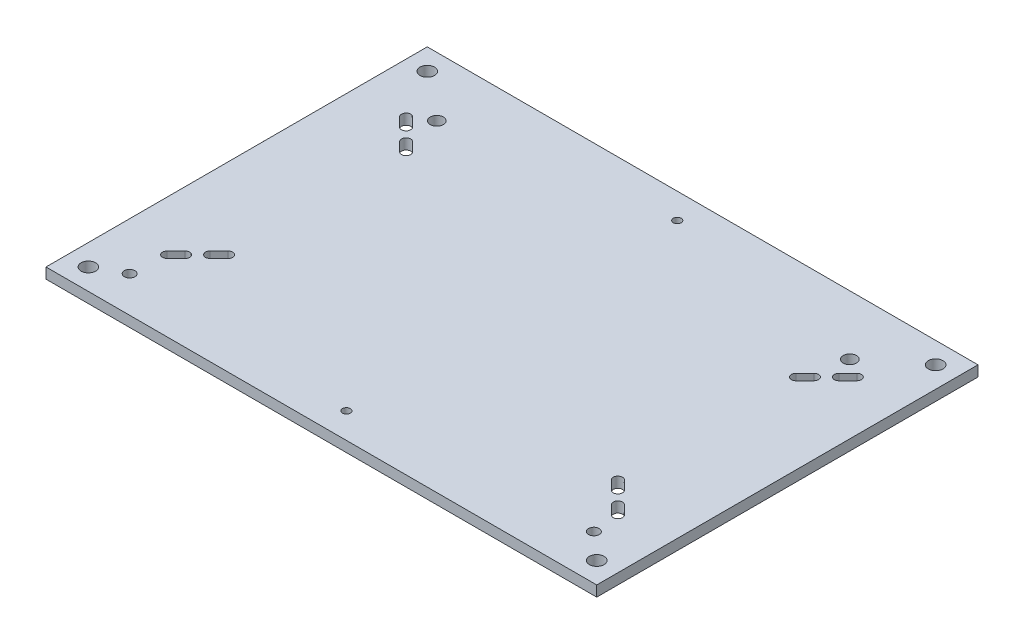
SolidWorks part; units mm, degrees
ref_plane "Front Plane" through (0, 0, 0) normal (0, 0, 1) x (1, 0, 0)
ref_plane "Top Plane" through (0, 0, 0) normal (0, 1, 0) x (1, 0, 0)
ref_plane "Right Plane" through (0, 0, 0) normal (1, 0, 0) x (0, 0, -1)
sketch "Sketch1" plane through (0, 0, 0) normal (0, 1, 0) x (1, 0, 0)
  line L1 (0, 0) -> (330.2, 0)
  line L2 (0, 0) -> (0, -228.6)
  line L3 (0, -228.6) -> (330.2, -228.6)
  line L4 (330.2, 0) -> (330.2, -228.6)
  dimension "D1" = 330.2
  dimension "D2" = 228.6
extrude "base plate" add sketch "Sketch1" against normal blind 6.35
sketch "center lines" plane through (0, 0, 0) normal (0, 1, 0) x (1, 0, 0)
  line L0 (165.1, 0) -> (165.1, -228.6) construction
  line L1 (330.2, 0) -> (0, 0) construction
  line L2 (0, -228.6) -> (330.2, -228.6) construction
  line L3 (0, -114.3) -> (330.2, -114.3) construction
  line L4 (0, 0) -> (0, -228.6) construction
  line L5 (330.2, -228.6) -> (330.2, 0) construction
sketch "Sketch3" plane through (0, 0, 0) normal (0, 1, 0) x (1, 0, 0)
  line L0 (21.0672, -185.8525) -> (30.0475, -194.8328)
  line L1 (30.0475, -194.8328) -> (60.5804, -164.2999)
  line L2 (60.5804, -164.2999) -> (51.6001, -155.3196)
  line L3 (51.6001, -155.3196) -> (21.0672, -185.8525)
  line L4 (29.9612, -185.9388) -> (35.3494, -180.5506) construction
  line L5 (28.0167, -183.9942) -> (33.4048, -178.6061)
  line L6 (31.9058, -187.8833) -> (37.2939, -182.4952)
  line L7 (0, -228.6) -> (330.2, -228.6) construction
  line L8 (48.2187, -167.6813) -> (42.8306, -173.0694) construction
  line L9 (50.1633, -169.6258) -> (44.7751, -175.014)
  line L10 (165.1, 0) -> (165.1, -228.6) construction
  line L11 (0, -114.3) -> (330.2, -114.3) construction
  line L12 (60.5804, -64.3001) -> (51.6001, -73.2804)
  line L13 (30.0475, -33.7672) -> (60.5804, -64.3001)
  line L14 (21.0672, -42.7475) -> (30.0475, -33.7672)
  line L15 (51.6001, -73.2804) -> (21.0672, -42.7475)
  line L16 (300.1525, -33.7672) -> (269.6196, -64.3001)
  line L17 (309.1328, -42.7475) -> (300.1525, -33.7672)
  line L18 (278.5999, -73.2804) -> (309.1328, -42.7475)
  line L19 (269.6196, -64.3001) -> (278.5999, -73.2804)
  line L20 (269.6196, -164.2999) -> (278.5999, -155.3196)
  line L21 (300.1525, -194.8328) -> (269.6196, -164.2999)
  line L22 (309.1328, -185.8525) -> (300.1525, -194.8328)
  line L23 (278.5999, -155.3196) -> (309.1328, -185.8525)
  line L24 (46.2742, -165.7367) -> (40.886, -171.1249)
  line L25 (29.9612, -42.6612) -> (35.3494, -48.0494) construction
  line L26 (28.0167, -44.6058) -> (33.4048, -49.9939)
  line L27 (31.9058, -40.7167) -> (37.2939, -46.1048)
  line L28 (48.2187, -60.9187) -> (42.8306, -55.5306) construction
  line L29 (50.1633, -58.9742) -> (44.7751, -53.586)
  line L30 (46.2742, -62.8633) -> (40.886, -57.4751)
  line L31 (300.2388, -42.6612) -> (294.8506, -48.0494) construction
  line L32 (302.1833, -44.6058) -> (296.7952, -49.9939)
  line L33 (298.2942, -40.7167) -> (292.9061, -46.1048)
  line L34 (281.9813, -60.9187) -> (287.3694, -55.5306) construction
  line L35 (280.0367, -58.9742) -> (285.4249, -53.586)
  line L36 (283.9258, -62.8633) -> (289.314, -57.4751)
  line L37 (281.9813, -167.6813) -> (287.3694, -173.0694) construction
  line L38 (280.0367, -169.6258) -> (285.4249, -175.014)
  line L39 (283.9258, -165.7367) -> (289.314, -171.1249)
  line L40 (300.2388, -185.9388) -> (294.8506, -180.5506) construction
  line L41 (302.1833, -183.9942) -> (296.7952, -178.6061)
  line L42 (298.2942, -187.8833) -> (292.9061, -182.4952)
  line L43 (51.6001, -164.2999) -> (51.6001, -155.3196)
  line L44 (60.5804, -164.2999) -> (51.6001, -164.2999)
  line L45 (51.6001, -64.3001) -> (51.6001, -73.2804)
  line L46 (60.5804, -64.3001) -> (51.6001, -64.3001)
  line L47 (278.5999, -64.3001) -> (278.5999, -73.2804)
  line L48 (269.6196, -64.3001) -> (278.5999, -64.3001)
  line L49 (278.5999, -164.2999) -> (278.5999, -155.3196)
  line L50 (269.6196, -164.2999) -> (278.5999, -164.2999)
  arc A0 (28.0167, -183.9942) -> (31.9058, -187.8833) centre (29.9612, -185.9388) ccw
  arc A1 (37.2939, -182.4952) -> (33.4048, -178.6061) centre (35.3494, -180.5506) ccw
  arc A2 (50.1633, -169.6258) -> (46.2742, -165.7367) centre (48.2187, -167.6813) ccw
  arc A3 (40.886, -171.1249) -> (44.7751, -175.014) centre (42.8306, -173.0694) ccw
  arc A4 (28.0167, -44.6058) -> (31.9058, -40.7167) centre (29.9612, -42.6612) cw
  arc A5 (37.2939, -46.1048) -> (33.4048, -49.9939) centre (35.3494, -48.0494) cw
  arc A6 (50.1633, -58.9742) -> (46.2742, -62.8633) centre (48.2187, -60.9187) cw
  arc A7 (40.886, -57.4751) -> (44.7751, -53.586) centre (42.8306, -55.5306) cw
  arc A8 (302.1833, -44.6058) -> (298.2942, -40.7167) centre (300.2388, -42.6612) ccw
  arc A9 (292.9061, -46.1048) -> (296.7952, -49.9939) centre (294.8506, -48.0494) ccw
  arc A10 (280.0367, -58.9742) -> (283.9258, -62.8633) centre (281.9813, -60.9187) ccw
  arc A11 (289.314, -57.4751) -> (285.4249, -53.586) centre (287.3694, -55.5306) ccw
  arc A12 (280.0367, -169.6258) -> (283.9258, -165.7367) centre (281.9813, -167.6813) cw
  arc A13 (289.314, -171.1249) -> (285.4249, -175.014) centre (287.3694, -173.0694) cw
  arc A14 (302.1833, -183.9942) -> (298.2942, -187.8833) centre (300.2388, -185.9388) cw
  arc A15 (292.9061, -182.4952) -> (296.7952, -178.6061) centre (294.8506, -180.5506) cw
  point P29 (32.6553, -183.2447)
  point P36 (45.5246, -170.3754)
  point P44 (32.6553, -45.3553)
  point P51 (45.5246, -58.2246)
  point P58 (297.5447, -45.3553)
  point P65 (284.6754, -58.2246)
  point P72 (284.6754, -170.3754)
  point P79 (297.5447, -183.2447)
  point P84 (37.2939, -178.6061)
  point P85 (40.886, -175.014)
  dimension "D6" = 2.75
  dimension "D10" = 5.08
  dimension "D9" = 2.032
  dimension "D1" = 43.18
  dimension "D2" = 12.7
  dimension "D3" = 45
  dimension "D4" = 99.9998
  dimension "D5" = 226.9998
  dimension "D7" = 7.62
  dimension "D8" = 6.35
extrude "slots" cut sketch "Sketch3" against normal through all contours A5 L27 A4 L26 | L33 A9 L32 A8 | L36 A11 L35 A10 | A13 L39 A12 L38 | A15 L42 A14 L41 | L6 A1 L5 A0 | L24 A3 L9 A2 | L30 A7 L29 A6 region at (32.6553, 0, 45.3553) region at (297.5447, 0, 45.3553) region at (284.6754, 0, 58.2246) region at (284.6754, 0, 170.3754) region at (297.5447, 0, 183.2447)
sketch "location of ESD" plane through (0, 0, 0) normal (0, 1, 0) x (1, 0, 0)
  line L0 (330.2, -228.6) -> (330.2, 0) construction
  line L1 (330.2, 0) -> (0, 0) construction
  point P0 (304.8, -114.3)
  point P3 (330.2, -114.3)
  dimension "D1" = 25.4
  dimension "D2" = 114.3
hole_wizard "Feet connection hole" positions "Sketch6" profile "Sketch7" hole size "1/4-20" standard "PEM® Inch" end condition through all
sketch "Sketch6" plane through (0, 0, 0) normal (0, 1, 0) x (1, 0, 0)
  line L0 (0, -228.6) -> (330.2, -228.6) construction
  line L1 (0, 0) -> (0, -228.6) construction
  line L2 (330.2, -228.6) -> (330.2, 0) construction
  line L3 (330.2, 0) -> (0, 0) construction
  point P3 (12.7, -215.9)
  point P19 (317.5, -12.7)
  point P31 (317.5, -215.9)
  point P33 (12.7, -12.7)
  dimension "D1" = 12.7
  dimension "D2" = 12.7
  dimension "D3" = 12.7
  dimension "D4" = 12.7
sketch "Sketch7" plane through (12.7, 0, 215.9) normal (1, 0, 0) x (0, 0, 1)
  line L0 (0, 0) -> (0, 6.35)
  line L1 (0, 6.35) -> (4.3688, 6.35)
  line L2 (4.3688, 6.35) -> (4.3688, 0)
  line L5 (4.3688, 0) -> (0, 0)
  line L11 (0, -6.35) -> (0, 107.95) construction
  dimension "Thru Hole Dia." = 8.7376
  dimension "Thru Hole Depth" = 6.35
sketch "Vacuum Chamber base hole locations" plane through (0, 0, 0) normal (0, 1, 0) x (1, 0, 0)
  line L2 (330.2, -228.6) -> (330.2, 0) construction
  line L4 (330.2, 0) -> (0, 0) construction
  point P0 (41.275, -35.56)
  point P1 (288.925, -35.56)
  point P2 (301.625, -201.7266)
  point P3 (28.575, -207.01)
  dimension "D1" = 247.65
  dimension "D2" = 12.7
  dimension "D3" = 12.7
  dimension "D4" = 171.45
  dimension "D5" = 28.575
  dimension "D6" = 35.56
  dimension "D7" = 0
hole_wizard "1/4 (0.25) Diameter Hole1" positions "Sketch9" profile "Sketch10" hole size "1/4" standard "ANSI Inch" end condition through all
sketch "Sketch9" plane through (0, 0, 0) normal (0, 1, 0) x (1, 0, 0)
  point P0 (28.575, -207.01)
  point P3 (301.625, -201.7266)
sketch "Sketch10" plane through (28.575, 0, 207.01) normal (1, 0, 0) x (0, 0, 1)
  line L0 (0, 0) -> (0, 6.35)
  line L1 (0, 6.35) -> (3.175, 6.35)
  line L2 (3.175, 6.35) -> (3.175, 0)
  line L5 (3.175, 0) -> (0, 0)
  line L11 (0, -6.35) -> (0, 107.95) construction
  dimension "Thru Hole Dia." = 6.35
  dimension "Thru Hole Depth" = 6.35
hole_wizard "5/16 (0.3125) Diameter Hole1" positions "Sketch11" profile "Sketch12" hole size "5/16" standard "ANSI Inch" end condition through all
sketch "Sketch11" plane through (0, 0, 0) normal (0, 1, 0) x (1, 0, 0)
  point P0 (41.275, -35.56)
  point P3 (288.925, -35.56)
sketch "Sketch12" plane through (41.275, 0, 35.56) normal (1, 0, 0) x (0, 0, 1)
  line L0 (0, 0) -> (0, 6.35)
  line L1 (0, 6.35) -> (3.9687, 6.35)
  line L2 (3.9687, 6.35) -> (3.9687, 0)
  line L5 (3.9687, 0) -> (0, 0)
  line L11 (0, -6.35) -> (0, 107.95) construction
  dimension "Thru Hole Dia." = 7.9375
  dimension "Thru Hole Depth" = 6.35
sketch "Sketch14" plane through (0, 0, 0) normal (0, 1, 0) x (1, 0, 0)
  line L2 (0, 0) -> (0, -228.6) construction
  line L3 (330.2, 0) -> (0, 0) construction
  line L4 (0, -228.6) -> (330.2, -228.6) construction
  point P0 (165.1, -15.24)
  point P1 (165.1, -213.36)
  point P8 (0, 0)
  dimension "D1" = 165.1
  dimension "D2" = 15.24
  dimension "D3" = 165.1
  dimension "D4" = 15.24
hole_wizard "ESD Connection hole" positions "Sketch15" profile "Sketch16" hole size "#6-32" standard "PEM® Inch" end condition through all
sketch "Sketch15" plane through (0, 0, 0) normal (0, 1, 0) x (1, 0, 0)
  point P0 (165.1, -15.24)
  point P3 (164.7687, -213.267)
sketch "Sketch16" plane through (165.1, 0, 15.24) normal (1, 0, 0) x (0, 0, 1)
  line L0 (0, 0) -> (0, 6.35)
  line L1 (0, 6.35) -> (2.3812, 6.35)
  line L2 (2.3812, 6.35) -> (2.3812, 0)
  line L5 (2.3812, 0) -> (0, 0)
  line L11 (0, -6.35) -> (0, 107.95) construction
  dimension "Thru Hole Dia." = 4.7625
  dimension "Thru Hole Depth" = 6.35
